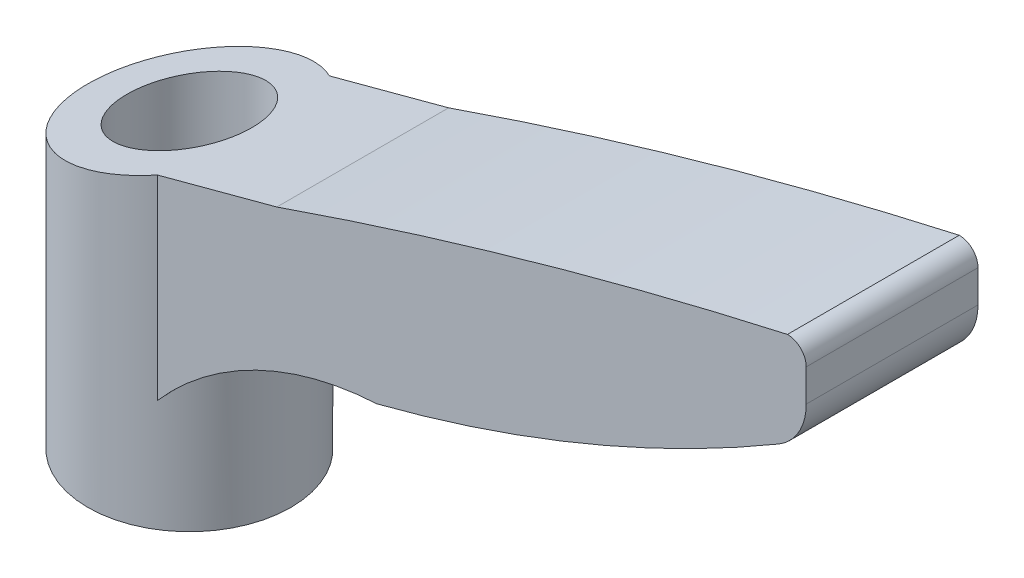
SolidWorks part; units mm, degrees
ref_plane "前视基准面" through (0, 0, 0) normal (0, 0, 1) x (1, 0, 0)
ref_plane "上视基准面" through (0, 0, 0) normal (0, 1, 0) x (1, 0, 0)
ref_plane "右视基准面" through (0, 0, 0) normal (1, 0, 0) x (0, 0, -1)
ref_plane "基准面4" through (0, 0, 0) normal (0, 0, 1) x (1, 0, 0)
sketch "草图1" plane through (0, 0, 0) normal (0, 0, 1) x (1, 0, 0)
  line L0 (0, 29.8) -> (6.5, 29.8)
  line L1 (6.5, 29.8) -> (6.5, 4)
  line L2 (6.5, 4) -> (0, 4)
  line L3 (0, 4) -> (0, 29.8)
  line L4 (0, 4) -> (0, 29.8) construction
revolve "旋转1" add sketch "草图1" angle 360 about L4 reverse direction yes
sketch "草图2" plane through (0, 0, 0) normal (0, 0, 1) x (1, 0, 0)
  line L0 (0, 35) -> (0, 6)
  line L1 (0, 6) -> (0.1937, 6)
  line L2 (45, 31.7346) -> (45, 35)
  line L3 (45, 35) -> (0, 35)
  arc A0 (0.1937, 6) -> (17.5, 18) centre (18.5357, -1.9732) cw
  arc A1 (17.5, 18) -> (43.2246, 28.6312) centre (-7.4599, 114.8349) ccw
  arc A2 (43.2246, 28.6312) -> (45, 31.7346) centre (41.4, 31.7346) ccw
extrude "凸台-拉伸1" add sketch "草图2" against normal blind 5.5 and the other way blind 5.5
ref_plane "基准面5" through (0, 0, 0) normal (0, 0, 1) x (1, 0, 0)
sketch "草图3" plane through (0, 0, 0) normal (0, 0, 1) x (1, 0, 0)
  line L0 (-6.5, 45) -> (-6.5, 21)
  line L1 (-6.5, 21) -> (11.1, 25.7159)
  line L2 (45, 33.8) -> (45, 45)
  line L3 (45, 45) -> (-6.5, 45)
  arc A0 (11.1, 25.7159) -> (43.8, 35) centre (109.2552, -257.7723) cw
  arc A1 (43.8, 35) -> (45, 33.8) centre (43.8, 33.8) cw
extrude "切除-拉伸1" cut sketch "草图3" along normal blind 7.5 and the other way blind 7.5
sketch "草图4" plane through (0, 0, 0) normal (0, 0, 1) x (1, 0, 0)
  line L0 (0, 0) -> (-5, 0)
  line L1 (-5, 0) -> (-5, 9.4)
  line L2 (-5, 9.4) -> (-4, 9.4)
  line L3 (-4, 9.4) -> (-4, 25.8)
  line L4 (-4, 25.8) -> (0, 25.8)
  line L5 (0, 25.8) -> (0, 0)
  line L6 (0, 50) -> (0, -50) construction
revolve "切除-旋转1" cut sketch "草图4" angle 360 about L6 reverse direction yes
ref_plane "B XY" through (0, 0, 0) normal (0, 1, 0) x (1, 0, 0)
ref_plane "B XZ" through (0, 0, 0) normal (0, 0, 1) x (1, 0, 0)
ref_plane "B YZ" through (0, 0, 0) normal (1, 0, 0) x (0, 0, -1)
ref_axis "B X" through (-80.9, 0, 0) along (1, 0, 0)
ref_axis "B Y" through (0, 0, 50) along (0, 0, -1)
ref_axis "B Z" through (0, 50, 0) along (0, -1, 0)
sketch3d "B"
  point P0 (0, 0, 0)
